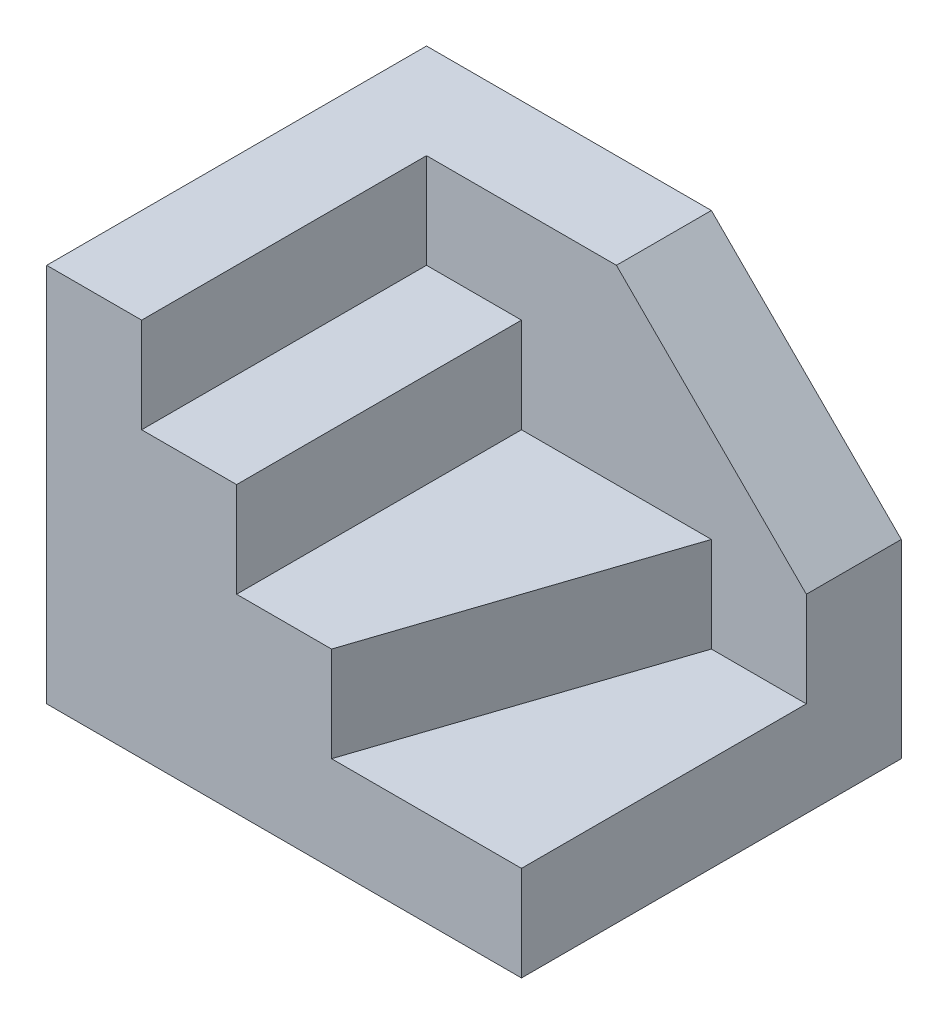
SolidWorks part; units mm, degrees
ref_plane "Front Plane" through (0, 0, 0) normal (0, 0, 1) x (1, 0, 0)
ref_plane "Top Plane" through (0, 0, 0) normal (0, 1, 0) x (1, 0, 0)
ref_plane "Right Plane" through (0, 0, 0) normal (1, 0, 0) x (0, 0, -1)
sketch "Sketch1" plane through (0, 0, 0) normal (0, 1, 0) x (1, 0, 0)
  line L0 (0, 0) -> (0, 40)
  line L1 (0, 40) -> (50, 40)
  line L2 (50, 40) -> (50, 0)
  line L3 (50, 0) -> (0, 0)
  line L4 (10, 0) -> (10, 30)
  line L5 (10, 30) -> (50, 30)
  line L6 (20, 30) -> (20, 0)
  line L7 (40, 30) -> (30, 0)
  dimension "D1" = 40
  dimension "D2" = 50
  dimension "D3" = 10
  dimension "D4" = 10
  dimension "D5" = 10
  dimension "D6" = 10
  dimension "D7" = 20
extrude "Boss-Extrude1" add sketch "Sketch1" along normal blind 40 contours L4 L5 L2 L1 L0 L3 region at (0.6403, 0, -20)
extrude "Boss-Extrude2" add sketch "Sketch1<3>" along normal blind 30 contours L6 L5 L4 L3 region at (15, 0, -15)
sketch "Sketch1<3>" plane through (0, 0, 0) normal (0, 1, 0) x (1, 0, 0) same geometry as "Sketch1"
extrude "Boss-Extrude3" add sketch "Sketch1<4>" along normal blind 20 contours L7 L5 L6 L3 region at (27.7778, 0, -16.6667)
sketch "Sketch1<4>" plane through (0, 0, 0) normal (0, 1, 0) x (1, 0, 0) same geometry as "Sketch1"
extrude "Boss-Extrude4" add sketch "Sketch1<5>" along normal blind 10 contours L5 L7 L3 L2 region at (42.2222, 0, -13.3333)
sketch "Sketch1<5>" plane through (0, 0, 0) normal (0, 1, 0) x (1, 0, 0) same geometry as "Sketch1"
sketch "Sketch2" plane through (0, 0, -30) normal (0, 0, 1) x (1, 0, 0)
  line L0 (30, 40) -> (50, 20)
  line L1 (10, 40) -> (50, 40) construction
  line L2 (50, 40) -> (50, 10) construction
  dimension "D1" = 20
  dimension "D2" = 45
extrude "Cut-Extrude1" cut sketch "Sketch2" against normal blind 10 and the other way through all contours L0
